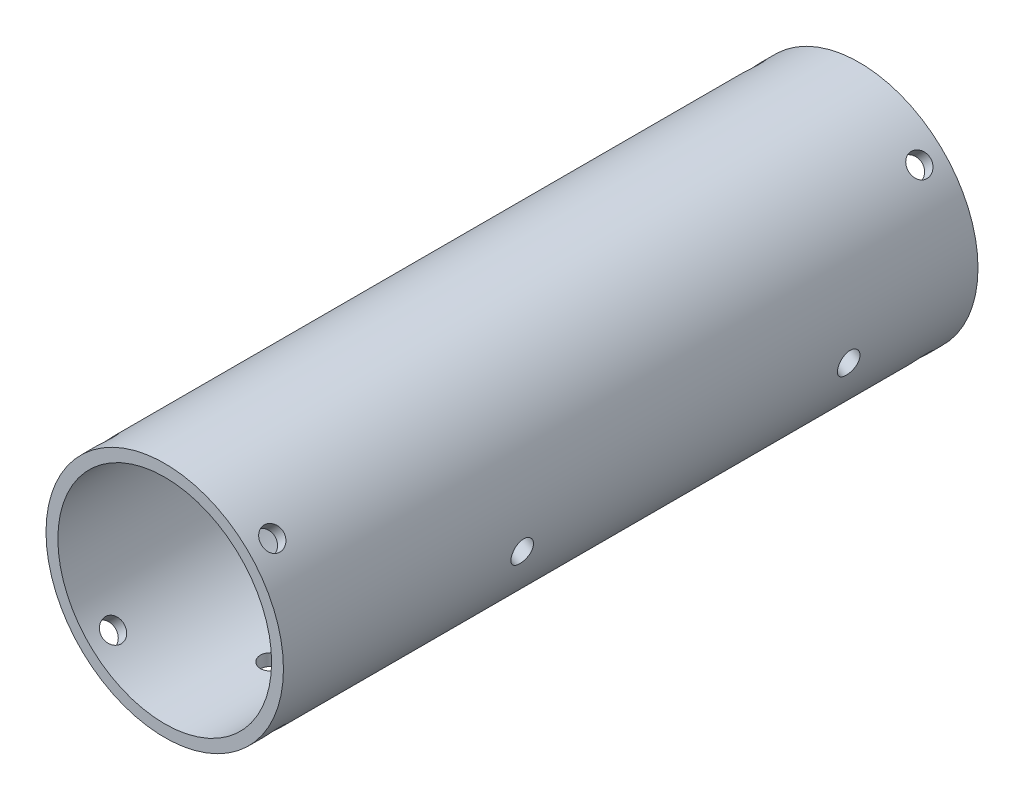
SolidWorks part; units mm, degrees
material "PET"
ref_plane "Front Plane" through (0, 0, 0) normal (0, 0, 1) x (1, 0, 0)
ref_plane "Top Plane" through (0, 0, 0) normal (0, 1, 0) x (1, 0, 0)
ref_plane "Right Plane" through (0, 0, 0) normal (1, 0, 0) x (0, 0, -1)
sketch "Sketch1" plane through (0, 0, 0) normal (0, 0, 1) x (1, 0, 0)
  circle A0 centre (0, 0) radius 20
  circle A1 centre (0, 0) radius 18
  dimension "D1" = 40
  dimension "D2" = 2
extrude "Boss-Extrude1" add sketch "Sketch1" along normal blind 100
ref_plane "Plane1" through (-17.3205, -10, 0) normal (-0.866, -0.5, 0) x (0, 0, -1)
sketch "Sketch3" plane through (-17.3205, -10, 0) normal (-0.866, -0.5, 0) x (0, 0, -1)
  line L0 (-100, 20) -> (-100, -20) construction
  line L1 (-100, -20) -> (0, -20) construction
  circle A0 centre (-67.5, -7) radius 1.875
  circle A1 centre (-12.5, -7) radius 1.875
  dimension "D1" = 3.75
  dimension "D2" = 32.5
  dimension "D3" = 13
  dimension "D4" = 2
extrude "Cut-Extrude1" cut sketch "Sketch3" against normal up to surface (2.745 mm away) up to face at (18, 0, 100)
mirror "Mirror1" about plane through (0, 0, 0) normal (1, 0, 0) of "Cut-Extrude1"
sketch "Sketch4" plane through (0, 0, 0) normal (0, 1, 0) x (1, 0, 0)
  line L0 (-20, -100) -> (20, -100) construction
  circle A0 centre (0, -90) radius 1.875
  dimension "D1" = 3.75
  dimension "D2" = 10
extrude "Cut-Extrude2" cut sketch "Sketch4" against normal blind 23
sketch "Sketch5" plane through (0, 0, 0) normal (0, 0, -1) x (-1, 0, 0)
  circle A0 centre (0, 0) radius 18
  circle A1 centre (0, 0) radius 20
  dimension "D1" = 2
extrude "Boss-Extrude2" add sketch "Sketch5" along normal blind 9
sketch "Sketch6" plane through (0, 0, 100) normal (0, 0, 1) x (1, 0, 0)
  circle A0 centre (0, 0) radius 18
  circle A1 centre (0, 0) radius 20
  dimension "D1" = 2
extrude "Boss-Extrude3" add sketch "Sketch6" along normal blind 8
ref_plane "Plane2" through (-14.1421, -14.1421, 0) normal (-0.7071, -0.7071, 0) x (0, 0, -1)
sketch "Sketch7" plane through (-14.1421, -14.1421, 0) normal (-0.7071, -0.7071, 0) x (0, 0, -1)
  line L0 (-108, 20) -> (-108, -20) construction
  circle A0 centre (-104, 0) radius 1.875
  dimension "D1" = 3.75
  dimension "D2" = 4
extrude "Cut-Extrude3" cut sketch "Sketch7" against normal up to next
pattern_circular "CirPattern1" count 4 over 360 about axis through (0, 0, 100) along (0, 0, -1) of "Cut-Extrude3"
ref_plane "Plane3" through (0, 0, 49.5) normal (0, 0, 1) x (1, 0, 0)
mirror "Mirror2" about plane through (0, 0, 49.5) normal (0, 0, 1) of "CirPattern1", "Cut-Extrude3"
